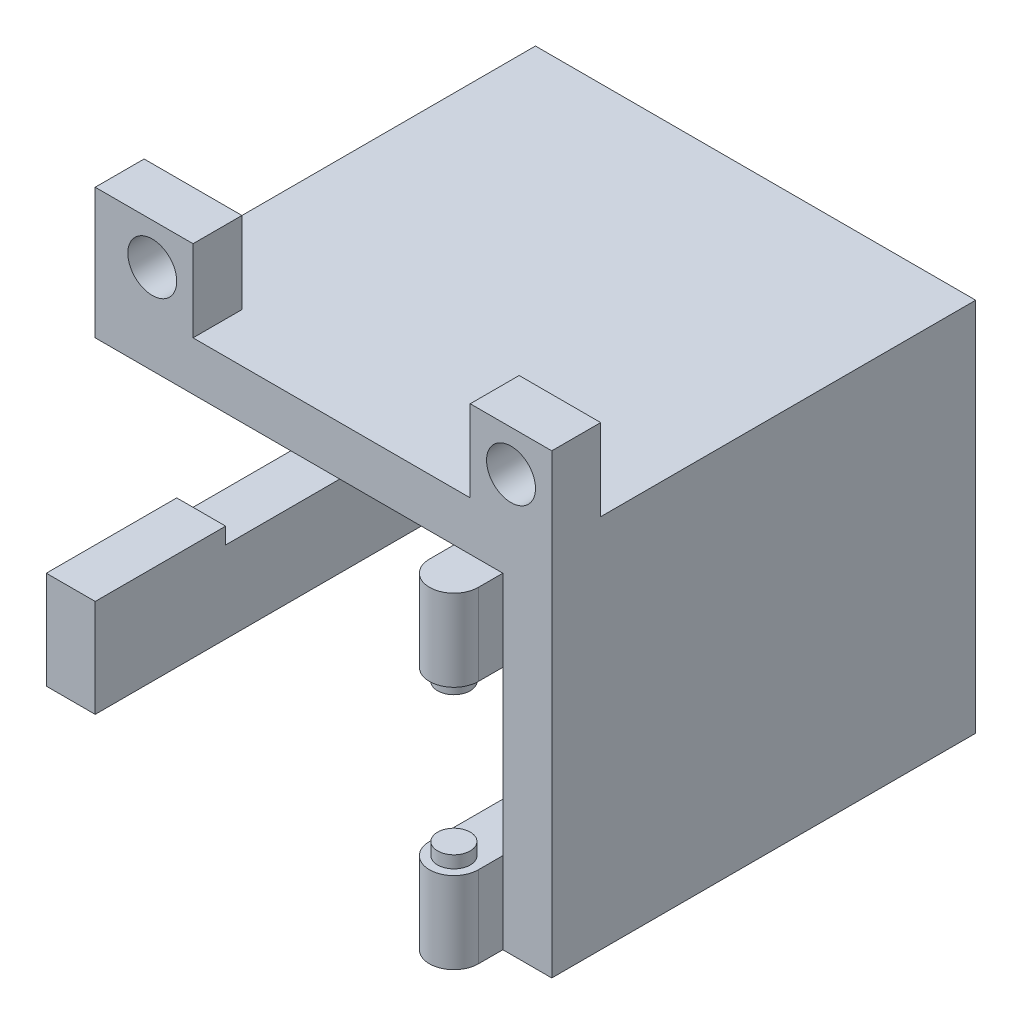
SolidWorks part; units mm, degrees
ref_plane "Alzado" through (0, 0, 0) normal (0, 0, 1) x (1, 0, 0)
ref_plane "Planta" through (0, 0, 0) normal (0, 1, 0) x (1, 0, 0)
ref_plane "Vista lateral" through (0, 0, 0) normal (1, 0, 0) x (0, 0, -1)
sketch "Croquis1" plane through (0, 0, 0) normal (0, 1, 0) x (1, 0, 0)
  line L1 (-15.5, -13) -> (15.5, -13)
  line L2 (-15.5, -13) -> (-15.5, 13)
  line L3 (-15.5, 13) -> (15.5, 13)
  line L4 (15.5, -13) -> (15.5, 13)
  line L5 (-15.5, -13) -> (15.5, 13) construction
  line L6 (-15.5, 13) -> (15.5, -13) construction
  point P0 (0, 0)
  dimension "D1" = 26
  dimension "D2" = 31
extrude "Saliente-Extruir1" add sketch "Croquis1" along normal blind 23
sketch "Croquis2" plane through (0, 0, 13) normal (0, 0, 1) x (1, 0, 0)
  line L0 (-15.5, 0) -> (15.5, 0) construction
  line L1 (-12.5, 20) -> (12.5, 20)
  line L2 (-12.5, 20) -> (-12.5, 0)
  line L3 (-12.5, 0) -> (12.5, 0)
  line L4 (12.5, 20) -> (12.5, 0)
  line L5 (-15.5, 23) -> (-15.5, 0) construction
  dimension "D1" = 3
  dimension "D2" = 25
  dimension "D3" = 20
extrude "Cortar-Extruir1" cut sketch "Croquis2" against normal blind 23
sketch "Croquis5" plane through (0, 0, 13) normal (0, 0, 1) x (1, 0, 0)
  line L9 (-15.5, 23) -> (15.5, 23) construction
  line L14 (-15.5, 23) -> (-11.5, 23)
  line L15 (-15.5, 23) -> (-15.5, 5)
  line L16 (-15.5, 5) -> (-11.5, 5)
  line L17 (-11.5, 23) -> (-11.5, 20)
  line L18 (-11.5, 20) -> (-9.5, 20)
  line L20 (-11.5, 11) -> (-9.5, 11)
  line L21 (-9.5, 20) -> (-9.5, 11)
  line L22 (-11.5, 11) -> (-11.5, 5)
  dimension "D1" = 4
  dimension "D2" = 18
  dimension "D3" = 2
  dimension "D4" = 9
  dimension "D5" = 3
extrude "Cortar-Extruir3" cut sketch "Croquis5" against normal up to next
sketch "Croquis6" plane through (0, 0, 13) normal (0, 0, 1) x (1, 0, 0)
  line L1 (-11.5, 23) -> (-6.5, 23)
  line L2 (-11.5, 23) -> (-11.5, 28)
  line L3 (-11.5, 28) -> (-6.5, 28)
  line L4 (-6.5, 23) -> (-6.5, 28)
  line L5 (15.5, 23) -> (10.5, 23)
  line L6 (15.5, 23) -> (15.5, 28)
  line L7 (15.5, 28) -> (10.5, 28)
  line L8 (10.5, 23) -> (10.5, 28)
  dimension "D1" = 5
extrude "Saliente-Extruir2" add sketch "Croquis6" against normal blind 3
sketch "Croquis7" plane through (0, 0, 13) normal (0, 0, 1) x (1, 0, 0)
  line L0 (-11.5, 28) -> (-6.5, 23) construction
  line L1 (10.5, 23) -> (15.5, 28) construction
  circle A0 centre (-9, 25.5) radius 1.5
  circle A1 centre (13, 25.5) radius 1.5
  dimension "D1" = 3
  dimension "D2" = 3
extrude "Cortar-Extruir4" cut sketch "Croquis7" against normal blind 3
sketch "Croquis8" plane through (0, 5, 0) normal (0, 1, 0) x (1, 0, 0)
  line L0 (-12.5, -13) -> (-12.5, 10) construction
  line L1 (-15.5, -13) -> (-12.5, -13)
  line L2 (-15.5, -13) -> (-15.5, -5)
  line L3 (-15.5, -5) -> (-12.5, -5)
  line L4 (-12.5, -13) -> (-12.5, -5)
  dimension "D1" = 8
extrude "Saliente-Extruir3" add sketch "Croquis8" along normal blind 1
sketch "Croquis9" plane through (-11.5, 0, 0) normal (-1, 0, 0) x (0, 0, 1)
  line L0 (10, 23) -> (10, 28)
  line L1 (10, 28) -> (13, 28)
  line L2 (13, 28) -> (13, 20)
  line L3 (13, 20) -> (5, 20)
  line L4 (-13, 20) -> (13, 20) construction
  line L5 (5, 20) -> (5, 23)
  line L6 (-13, 23) -> (10, 23) construction
  line L7 (5, 23) -> (10, 23)
  dimension "D1" = 8
extrude "Saliente-Extruir4" add sketch "Croquis9" along normal blind 1
sketch "Croquis10" plane through (0, 0, 0) normal (0, -1, 0) x (1, 0, 0)
  line L0 (9.5, 10) -> (9.5, 13)
  line L1 (12.5, 13) -> (9.5, 13) construction
  line L2 (12.5, 13) -> (12.5, 10)
  line L3 (12.5, 10) -> (9.5, 10)
  line L4 (9.5, 13) -> (9.5, 14.5)
  line L5 (12.5, 13) -> (12.5, 14.5)
  arc A0 (12.5, 14.5) -> (9.5, 14.5) centre (11, 14.5) ccw
  dimension "D2" = 1.5
  dimension "D1" = 3
extrude "Saliente-Extruir5" add sketch "Croquis10" against normal blind 5
sketch "Croquis12" plane through (0, 5, 0) normal (0, 1, 0) x (1, 0, 0)
  circle A0 centre (11, -14.5) radius 1
  arc A3 (9.5, -14.5) -> (12.5, -14.5) centre (11, -14.5) ccw construction
  dimension "D1" = 2
extrude "Saliente-Extruir7" add sketch "Croquis12" along normal blind 0.75
ref_plane "Plano1" through (0, 10, 0) normal (0, -1, 0) x (-1, 0, 0)
mirror "Simetría1" about plane through (0, 10, 0) normal (0, -1, 0) of "Saliente-Extruir7", "Saliente-Extruir5"
